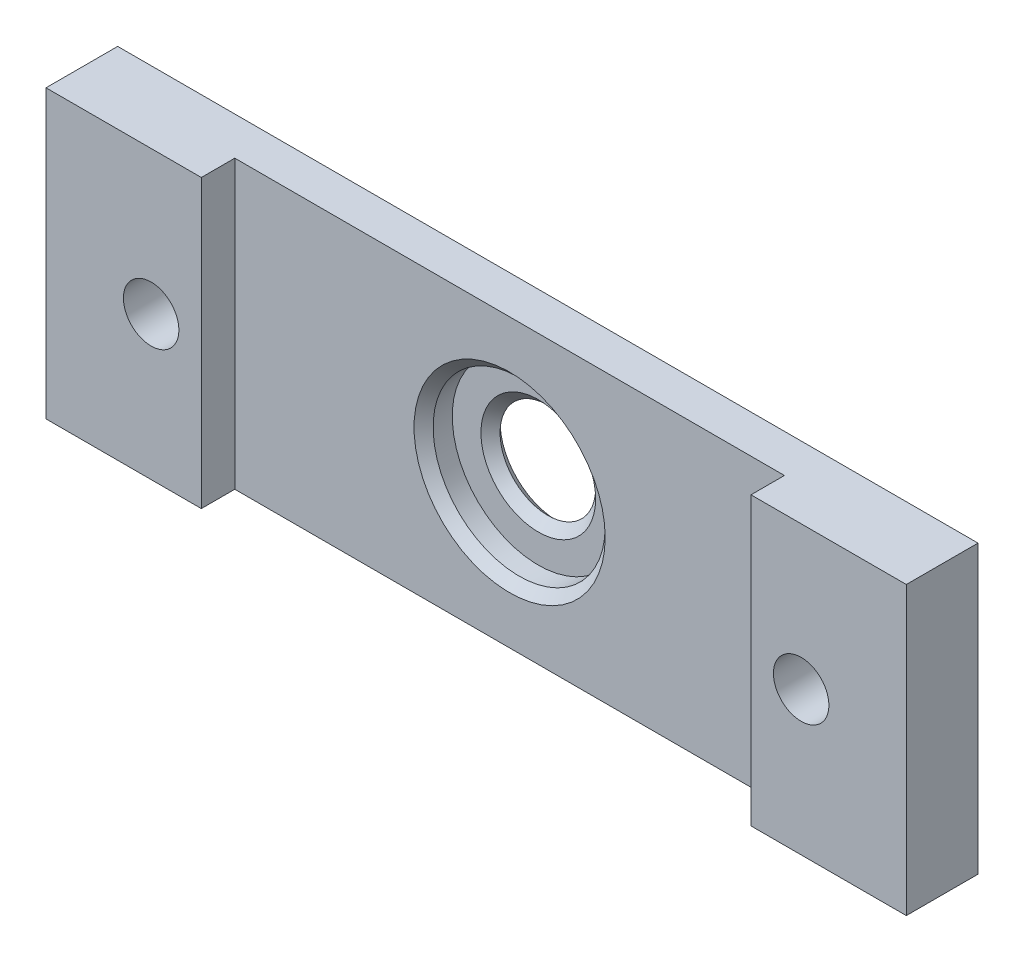
SolidWorks part; units mm, degrees
ref_plane "前视基准面" through (0, 0, 0) normal (0, 0, 1) x (1, 0, 0)
ref_plane "上视基准面" through (0, 0, 0) normal (0, 1, 0) x (1, 0, 0)
ref_plane "右视基准面" through (0, 0, 0) normal (1, 0, 0) x (0, 0, -1)
other "Configuration Table"
sketch "草图1" plane through (0, 0, 0) normal (0, 0, 1) x (1, 0, 0)
  line L1 (-45, 15) -> (45, 15)
  line L2 (-45, 15) -> (-45, -15)
  line L3 (-45, -15) -> (45, -15)
  line L4 (45, 15) -> (45, -15)
  dimension "D1" = 90
  dimension "D2" = 45
  dimension "D3" = 30
  dimension "D4" = 15
extrude "凸台-拉伸1" add sketch "草图1" along normal blind 5
sketch "草图2" plane through (0, 0, 5) normal (0, 0, 1) x (1, 0, 0)
  line L0 (45, 15) -> (-45, 15) construction
  line L1 (45, -15) -> (28.75, -15)
  line L2 (45, -15) -> (45, 15)
  line L3 (45, 15) -> (28.75, 15)
  line L4 (28.75, -15) -> (28.75, 15)
  line L6 (-45, -15) -> (-28.75, -15)
  line L7 (-45, -15) -> (-45, 15)
  line L8 (-45, 15) -> (-28.75, 15)
  line L9 (-28.75, -15) -> (-28.75, 15)
  dimension "D1" = 57.5
  dimension "D2" = 28.75
extrude "凸台-拉伸2" add sketch "草图2" along normal blind 3.5
sketch "草图3" plane through (0, 0, 0) normal (0, 0, -1) x (-1, 0, 0)
  circle A0 centre (34, 0) radius 2.9
  circle A1 centre (-34, 0) radius 2.9
  dimension "D1" = 5.8
  dimension "D2" = 5.8
  dimension "D3" = 34
  dimension "D4" = 34
extrude "切除-拉伸1" cut sketch "草图3" against normal through all both and the other way through all
chamfer "倒角1" distance 1 angle 45 6 edges at (-45, 0, 0) (0, 15, 0) (45, 0, 0) (0, -15, 0) (36.9, 0, 0) (-31.1, 0, 0)
sketch "草图4" plane through (0, 0, 5) normal (0, 0, 1) x (1, 0, 0)
  circle A0 centre (0, 0) radius 9
  dimension "D1" = 18
extrude "切除-拉伸2" cut sketch "草图4" against normal blind 3 and the other way through all
chamfer "倒角2" distance 1 angle 45 1 edges at (9, 0, 5)
sketch "草图5" plane through (0, 0, 2) normal (0, 0, 1) x (1, 0, 0)
  circle A0 centre (0, 0) radius 5
  dimension "D1" = 10
extrude "切除-拉伸3" cut sketch "草图5" against normal through all both and the other way through all
chamfer "倒角3" distance 1 angle 45 2 edges at (5, 0, 0) (5, 0, 2)
